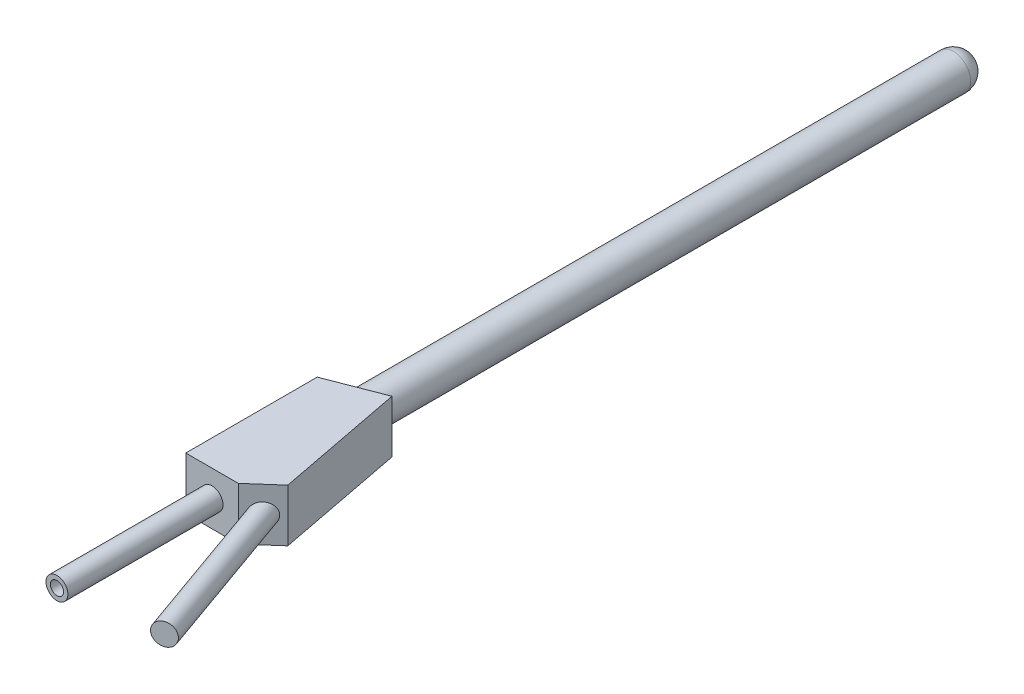
SolidWorks part; units mm, degrees
ref_plane "Front Plane" through (0, 0, 0) normal (0, 0, 1) x (1, 0, 0)
ref_plane "Top Plane" through (0, 0, 0) normal (0, 1, 0) x (1, 0, 0)
ref_plane "Right Plane" through (0, 0, 0) normal (1, 0, 0) x (0, 0, -1)
sketch "Sketch1" plane through (0, 0, 0) normal (0, 1, 0) x (1, 0, 0)
  line L0 (0, 0) -> (6.1582, 2.3741)
  line L1 (6.1582, 2.3741) -> (9, -12.3542)
  line L2 (9, -12.3542) -> (6, -15)
  line L3 (6, -15) -> (0, -15)
  line L4 (0, -15) -> (0, 0)
  point P3 (6, 2.6835)
  point P7 (0, 0)
  dimension "D1" = 15
  dimension "D2" = 6.6
  dimension "D3" = 15
  dimension "D4" = 6
  dimension "D5" = 9
  dimension "D6" = 4
extrude "Boss-Extrude1" add sketch "Sketch1" along normal blind 6
sketch "Sketch4" plane through (0, 0, 0) normal (0, 0, 1) x (1, 0, 0)
  line L0 (0, 0) -> (6.1582, 6) construction
  line L1 (0, 6) -> (6.1582, 0) construction
  circle A0 centre (3.0791, 3) radius 2
  point P10 (3.0791, 3)
  dimension "D1" = 4
extrude "Boss-Extrude2" add sketch "Sketch4" against normal blind 71.5
fillet "Fillet1" radius 2 1 edges at (5.0791, 3, -71.5)
sketch "Sketch5" plane through (0, 0, 15) normal (0, 0, 1) x (1, 0, 0)
  line L0 (0, 0) -> (6, 0) construction
  line L1 (0, 6) -> (0, 0) construction
  circle A0 centre (3, 3) radius 1.25
  dimension "D1" = 2.5
  dimension "D2" = 3
  dimension "D3" = 3
extrude "Boss-Extrude3" add sketch "Sketch5" along normal blind 17.7
shell "Shell1" thickness 0.5 removed face at (4.25, 3, 32.7)
sketch "Sketch6" plane through (0, 6, 0) normal (0, 1, 0) x (1, 0, 0)
  line L0 (2.3298, 0.8982) -> (7.5, -13.6771) construction
  line L1 (6, -15) -> (9, -12.3542) construction
  line L2 (6.1582, 2.3741) -> (0, 0) construction
  point P4 (3.7263, -1.8298)
  point P5 (0, 0)
  point P6 (3.2657, -1.8554)
  point P7 (3.2146, -2.1624)
  point P8 (2.1471, 0.8278)
  point P11 (2.3298, 0.8982)
ref_plane "Plane1" through (7.5, 6, 13.6771) normal (0.3343, 0, 0.9425) x (0.9425, 0, -0.3343)
sketch "Sketch7" plane through (7.5, 6, 13.6771) normal (0.3343, 0, 0.9425) x (0.9425, 0, -0.3343)
  line L0 (1.8559, 0) -> (1.8559, -6) construction
  line L2 (-1.8559, -6) -> (1.8559, -6) construction
  circle A0 centre (0.0009, -3) radius 1.25
  point P6 (0, 0)
  dimension "D1" = 2.5
  dimension "D2" = 1.855
  dimension "D3" = 3
extrude "Boss-Extrude4" add sketch "Sketch7" along normal blind 18.5
extrude "Boss-Extrude5" add sketch "Sketch7<2>" against normal blind 5
sketch "Sketch7<2>" plane through (7.5, 6, 13.6771) normal (0.3343, 0, 0.9425) x (0.9425, 0, -0.3343) same geometry as "Sketch7"
